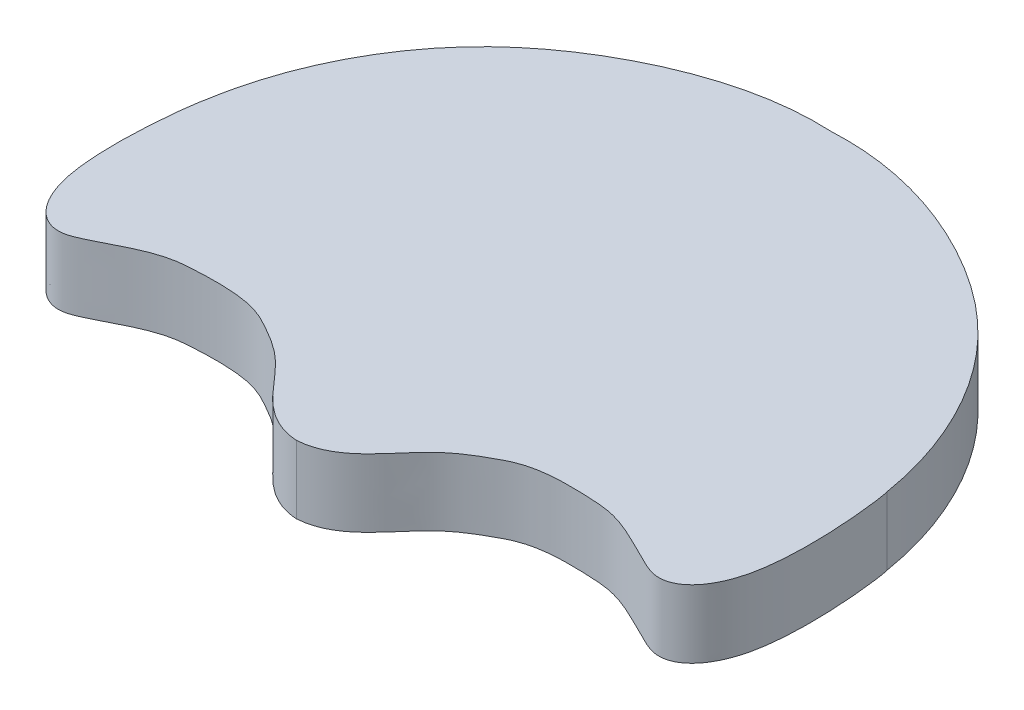
SolidWorks part; units mm, degrees
material "6061-T6 (SS)"
ref_plane "Front Plane" through (0, 0, 0) normal (0, 0, 1) x (1, 0, 0)
ref_plane "Top Plane" through (0, 0, 0) normal (0, 1, 0) x (1, 0, 0)
ref_plane "Right Plane" through (0, 0, 0) normal (1, 0, 0) x (0, 0, -1)
sketch "Sketch3" plane through (0, 0, 0) normal (0, 1, 0) x (1, 0, 0)
  line L0 (0, 0) -> (0, 159.1899) construction
  line L1 (0, 0) -> (0, -140.5301) construction
  line L2 (0, 0) -> (-190.5, 0) construction
  line L3 (0, 0) -> (190.5, 0) construction
  spline S0 degree 3 poles (-190.5, 0) (-184.3927, 37.537) (-157.2613, 93.9641) (-82.3875, 146.6227) (-31.3114, 160.7999) (0, 159.1899) knots 0 0 0 0 0.424401 0.65637 1 1 1 1
  spline S1 degree 3 poles (-190.5, 0) (-192.064, -4.9635) (-201.9672, -83.3146) (-174.6966, -109.29) (-151.6301, -100.568) (-131.4108, -87.7198) (-96.8436, -85.3754) (-78.6925, -86.2588) (-58.8335, -96.8794) (-37.3059, -109.9358) (-21.3496, -139.1148) (0, -140.5301) knots 0 0 0 0 0.166997 0.292321 0.319633 0.426735 0.458914 0.609242 0.64191 0.766802 1 1 1 1
  spline S2 degree 3 poles (190.5, 0) (192.064, -4.9635) (201.9672, -83.3146) (174.6966, -109.29) (151.6301, -100.568) (131.4108, -87.7198) (96.8436, -85.3754) (78.6925, -86.2588) (58.8335, -96.8794) (37.3059, -109.9358) (21.3496, -139.1148) (0, -140.5301) knots 0 0 0 0 0.166997 0.292321 0.319633 0.426735 0.458914 0.609242 0.64191 0.766802 1 1 1 1
  spline S3 degree 3 poles (190.5, 0) (184.3927, 37.537) (157.2613, 93.9641) (82.3875, 146.6227) (31.3114, 160.7999) (0, 159.1899) knots 0 0 0 0 0.424401 0.65637 1 1 1 1
  dimension "D1" = 381
  dimension "D2" = 299.72
  dimension "D3" = 159.1899
  dimension "D4" = 86.8953
  dimension "D5" = 104.4979
  dimension "D6" = 29.1616
  dimension "D7" = 92.2742
  dimension "D8" = 108.411
  dimension "D9" = 67.4883
  dimension "D10" = 43.7314
  dimension "D11" = 117.6915
  dimension "D12" = 162.2568
  dimension "D13" = 89.4522
  dimension "D14" = 140.1036
  dimension "D15" = 175.0666
  dimension "D16" = 50.2669
  dimension "D17" = 101.3666
  dimension "D18" = 138.1225
  dimension "D19" = 155.1557
  dimension "D20" = 192.0074
  dimension "D21" = 193.9268
  dimension "D23" = 76.6666
extrude "Boss-Extrude1" add sketch "Sketch3" along normal blind 38.1 from surface starting at plane "Top Plane"
sketch "Sketch5" plane through (0, 0, 0) normal (0, -1, 0) x (1, 0, 0)
  line L0 (0, 0) -> (0, -20.32) construction
  line L1 (31.75, -52.07) -> (-31.75, -52.07)
  line L2 (31.75, -52.07) -> (31.75, 11.43)
  line L3 (31.75, 11.43) -> (-31.75, 11.43)
  line L4 (-31.75, -52.07) -> (-31.75, 11.43)
  line L5 (31.75, -52.07) -> (-31.75, 11.43) construction
  line L6 (31.75, 11.43) -> (-31.75, -52.07) construction
  line L7 (-31.75, -52.07) -> (-31.75, -30.48)
  line L8 (-31.75, -30.48) -> (31.75, -30.48) construction
  line L9 (0, -20.32) -> (140.7253, -20.32) construction
  line L10 (0, -20.32) -> (0, -97.1287) construction
  line L11 (0, -20.32) -> (31.9753, -118.7297) construction
  line L13 (0, -20.32) -> (63.8443, -108.1942) construction
  line L14 (0, -20.32) -> (95.5392, -89.7333) construction
  line L15 (124.7166, -60.8429) -> (0, -20.32) construction
  line L16 (0, -20.32) -> (154.5508, 21.0918) construction
  line L17 (0, -20.32) -> (148.922, 65.6601) construction
  line L18 (0, -20.32) -> (-31.9753, -118.7297) construction
  line L19 (0, -20.32) -> (-63.8443, -108.1942) construction
  line L20 (0, -20.32) -> (-95.5392, -89.7333) construction
  line L21 (-124.7166, -60.8429) -> (0, -20.32) construction
  line L22 (0, -20.32) -> (-154.5508, 21.0918) construction
  line L23 (0, -20.32) -> (-148.922, 65.6601) construction
  spline S0 degree 3 poles (-148.922, 65.6601) (-157.8584, 40.2253) (-156.2837, 8.5854) (-143.1202, -28.9506) (-139.3242, -37.3463) (-130.3709, -53.1962) (-125.215, -60.649) (-118.0488, -69.1403) (-116.5795, -70.7975) (-113.5719, -74.0252) (-112.0368, -75.592) (-107.2801, -80.2116) (-103.9215, -83.1695) (-93.3361, -91.6595) (-85.5959, -96.8074) (-76.3408, -101.9556) (-75.3049, -102.5187) (-73.219, -103.6268) (-72.1677, -104.1726) (-69.0049, -105.7765) (-66.8862, -106.8006) (-60.5068, -109.7299) (-56.2231, -111.4921) (-47.6308, -114.6027) (-43.3223, -115.9511) (-34.7104, -118.209) (-30.4072, -119.1185) (-21.8242, -120.4791) (-17.5446, -120.9304) (-11.1443, -121.2499) (-9.0138, -121.2968) (-5.8216, -121.2757) (-4.1848, -121.2414) (-2.5489, -121.1705) (-1.9677, -121.1408) (-1.9605, -121.1404) (-1.2995, -121.1064) (-0.6497, -121.073) (0, -121.0396) knots -0.292878 -0.292878 -0.292878 -0.292878 0.125 0.125 0.25 0.25 0.375 0.375 0.40625 0.40625 0.4375 0.4375 0.5 0.5 0.625 0.625 0.640625 0.640625 0.65625 0.65625 0.6875 0.6875 0.75 0.75 0.8125 0.8125 0.875 0.875 0.9375 0.9375 0.96875 0.96875 0.984375 0.992798 0.992798 0.99292 0.99292 1 1 1 1
  spline S5 degree 3 poles (998.6789, -69.6893) (665.1581, -86.8384) (331.6156, -103.9885) (-1.9268, -121.1387) (-1.9605, -121.1404) (-1.9677, -121.1408) (-2.5489, -121.1705) (-4.1848, -121.2414) (-5.8216, -121.2757) (-9.0138, -121.2968) (-11.1443, -121.2499) (-17.5446, -120.9304) (-21.8242, -120.4791) (-30.4072, -119.1185) (-34.7104, -118.209) (-43.3223, -115.9511) (-47.6308, -114.6027) (-56.2231, -111.4921) (-60.5068, -109.7299) (-66.8862, -106.8006) (-69.0049, -105.7765) (-72.1677, -104.1726) (-73.219, -103.6268) (-75.3049, -102.5187) (-76.3408, -101.9556) (-85.5959, -96.8074) (-93.3361, -91.6595) (-103.9215, -83.1695) (-107.2801, -80.2116) (-112.0368, -75.592) (-113.5719, -74.0252) (-116.5795, -70.7975) (-118.0488, -69.1403) (-125.215, -60.649) (-130.3709, -53.1962) (-139.3242, -37.3463) (-143.1202, -28.9506) (-198.5095, 128.9933) (-22.362, 351.6373) (651.8169, -587.5188) knots -3.627409 -3.627409 -3.627409 -3.627409 0.006836 0.00708 0.00708 0.007202 0.007202 0.015625 0.03125 0.03125 0.0625 0.0625 0.125 0.125 0.1875 0.1875 0.25 0.25 0.3125 0.3125 0.34375 0.34375 0.359375 0.359375 0.375 0.375 0.5 0.5 0.5625 0.5625 0.59375 0.59375 0.625 0.625 0.75 0.75 0.875 0.875 3.034324 3.034324 3.034324 3.034324 only from (0, -121.0396) to (-152.8945, 6.1184)
  spline S6 degree 3 poles (-1687.8289, -2297.0686) (-150.4269, 537.0593) (218.9922, 187.4002) (143.1202, -28.9506) (139.3242, -37.3463) (130.3709, -53.1962) (125.215, -60.649) (118.0488, -69.1403) (116.5795, -70.7975) (113.5719, -74.0252) (112.0368, -75.592) (107.2801, -80.2116) (103.9215, -83.1695) (93.3361, -91.6595) (85.5959, -96.8074) (76.3408, -101.9556) (75.3049, -102.5187) (73.219, -103.6268) (72.1677, -104.1726) (69.0049, -105.7765) (66.8862, -106.8006) (60.5068, -109.7299) (56.2231, -111.4921) (47.6308, -114.6027) (43.3223, -115.9511) (34.7104, -118.209) (30.4072, -119.1185) (21.8242, -120.4791) (17.5446, -120.9304) (11.1443, -121.2499) (9.0138, -121.2968) (5.8216, -121.2757) (4.1848, -121.2414) (2.5489, -121.1705) (1.9677, -121.1408) (1.9605, -121.1404) (-997.3522, -69.7575) (-1996.6535, -18.3753) (-2996.029, 33.0152) knots -2.879056 -2.879056 -2.879056 -2.879056 0.125 0.125 0.25 0.25 0.375 0.375 0.40625 0.40625 0.4375 0.4375 0.5 0.5 0.625 0.625 0.640625 0.640625 0.65625 0.65625 0.6875 0.6875 0.75 0.75 0.8125 0.8125 0.875 0.875 0.9375 0.9375 0.96875 0.96875 0.984375 0.992798 0.992798 0.99292 0.99292 11.881939 11.881939 11.881939 11.881939 only from (152.8945, 6.1184) to (0, -121.0396)
  spline S8 degree 3 poles (148.922, 65.6601) (157.8584, 40.2253) (156.2837, 8.5854) (143.1202, -28.9506) (139.3242, -37.3463) (130.3709, -53.1962) (125.215, -60.649) (118.0488, -69.1403) (116.5795, -70.7975) (113.5719, -74.0252) (112.0368, -75.592) (107.2801, -80.2116) (103.9215, -83.1695) (93.3361, -91.6595) (85.5959, -96.8074) (76.3408, -101.9556) (75.3049, -102.5187) (73.219, -103.6268) (72.1677, -104.1726) (69.0049, -105.7765) (66.8862, -106.8006) (60.5068, -109.7299) (56.2231, -111.4921) (47.6308, -114.6027) (43.3223, -115.9511) (34.7104, -118.209) (30.4072, -119.1185) (21.8242, -120.4791) (17.5446, -120.9304) (11.1443, -121.2499) (9.0138, -121.2968) (5.8216, -121.2757) (4.1848, -121.2414) (2.5489, -121.1705) (1.9677, -121.1408) (1.9605, -121.1404) (1.2995, -121.1064) (0.6497, -121.073) (0, -121.0396) knots -0.292878 -0.292878 -0.292878 -0.292878 0.125 0.125 0.25 0.25 0.375 0.375 0.40625 0.40625 0.4375 0.4375 0.5 0.5 0.625 0.625 0.640625 0.640625 0.65625 0.65625 0.6875 0.6875 0.75 0.75 0.8125 0.8125 0.875 0.875 0.9375 0.9375 0.96875 0.96875 0.984375 0.992798 0.992798 0.99292 0.99292 1 1 1 1
  point P0 (0, -20.32)
  point P3 (0, -20.32)
  point P14 (0, 114.3)
  point P16 (0, 88.9)
  dimension "D1" = 20.32
  dimension "D2" = 63.5
  dimension "D3" = 63.5
  dimension "D4" = 21.59
  dimension "D6" = 25.4
  dimension "D7" = 88.9
  dimension "D8" = 18
  dimension "D9" = 18
  dimension "D10" = 18
  dimension "D11" = 18
  dimension "D12" = 15
  dimension "D13" = 15
  dimension "D5" = 38.1
equation "\"Plate thickness\"=1.5"
equation "\"D1@Boss-Extrude1\"=\"Plate thickness\""
equation "\"Bracket Alignment\"= .80"
equation "\"D1@Sketch5\"=\"Bracket Alignment\""
